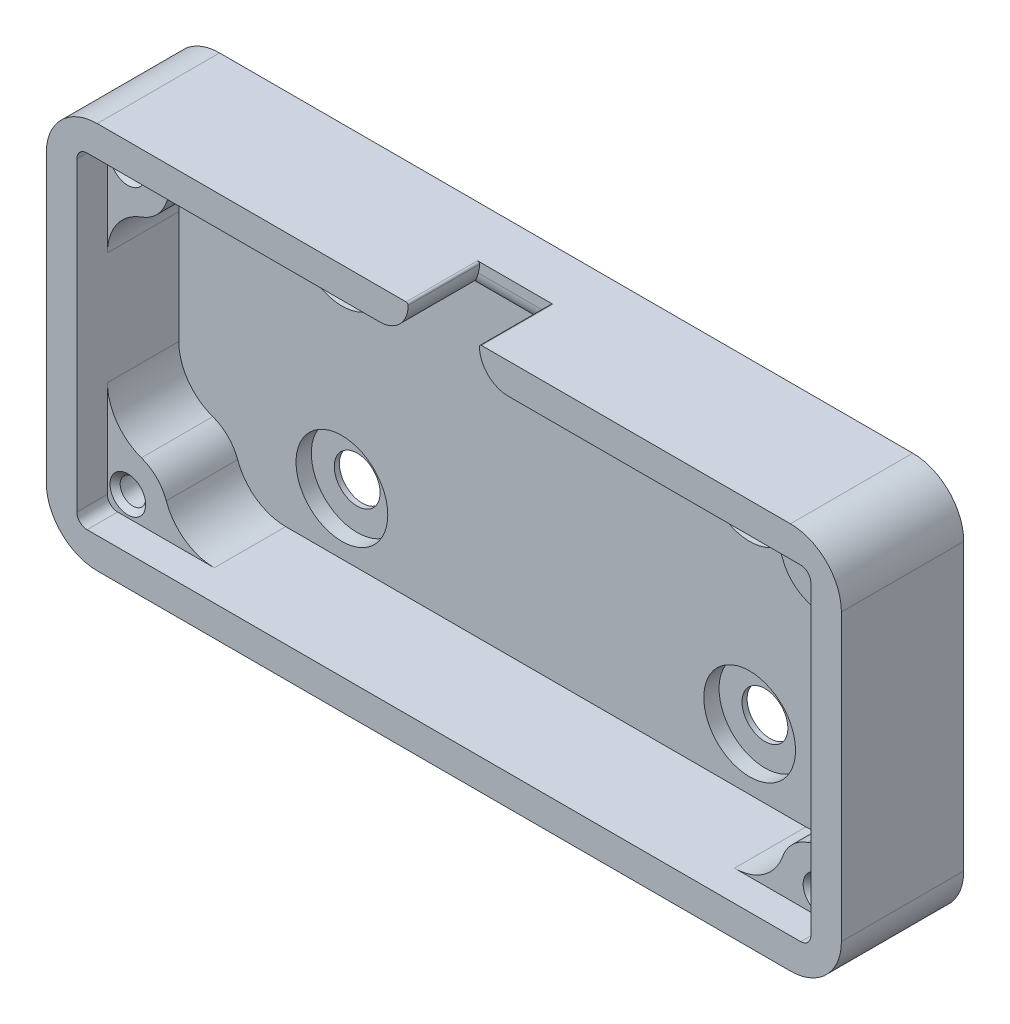
SolidWorks part; units mm, degrees
ref_plane "Piano frontale" through (0, 0, 0) normal (0, 0, 1) x (1, 0, 0)
ref_plane "Piano superiore" through (0, 0, 0) normal (0, 1, 0) x (1, 0, 0)
ref_plane "Piano destro" through (0, 0, 0) normal (1, 0, 0) x (0, 0, -1)
sketch "Schizzo1" plane through (0, 0, 0) normal (0, 0, 1) x (1, 0, 0)
  line L0 (-18.3021, 8.9164) -> (-39, 19) construction
  line L1 (36, 16) -> (-36, 16)
  line L2 (36, 16) -> (36, -16)
  line L3 (36, -16) -> (-36, -16)
  line L4 (-36, 16) -> (-36, -16)
  line L5 (36, 16) -> (19.0589, 8.4706) construction
  line L6 (36, -16) -> (-36, 16) construction
  line L7 (39, 19) -> (-39, 19)
  line L8 (39, 19) -> (39, -19)
  line L9 (39, -19) -> (-39, -19)
  line L10 (-39, 19) -> (-39, -19)
  line L11 (39, 19) -> (19.3371, 9.4206) construction
  line L12 (39, -19) -> (19.5274, -9.5133) construction
  line L13 (34, 14) -> (-34, 14)
  line L14 (34, 14) -> (34, -14)
  line L15 (34, -14) -> (-34, -14)
  line L16 (-34, 14) -> (-34, -14)
  line L17 (34, 14) -> (-34, -14) construction
  line L18 (34, -14) -> (-34, 14) construction
  line L24 (20, -10) -> (-20, -10) construction
  line L25 (20, -10) -> (20, 10) construction
  line L26 (20, 10) -> (-20, 10) construction
  line L27 (-18.8804, -9.1982) -> (-39, -19) construction
  line L28 (19.5274, -9.5133) -> (-18.3021, 8.9164) construction
  line L29 (19.3371, 9.4206) -> (-18.8804, -9.1982) construction
  line L30 (19.0589, 8.4706) -> (-36, -16) construction
  line L31 (-20, -10) -> (-20, 10) construction
  line L32 (20, -10) -> (-20, 10) construction
  line L33 (20, 10) -> (-20, -10) construction
  circle A0 centre (-34, 14) radius 1.25
  circle A1 centre (-34, -14) radius 1.25
  circle A2 centre (34, -14) radius 1.25
  circle A3 centre (34, 14) radius 1.25
  circle A8 centre (-20, 10) radius 2.25
  circle A9 centre (-20, -10) radius 2.25
  circle A10 centre (20, -10) radius 2.25
  circle A11 centre (20, 10) radius 2.25
  point P0 (0, 0)
  point P6 (0, 0)
  point P19 (0, 0)
  point P28 (1.4654, -0.5401)
  point P32 (0, 0)
  dimension "D5" = 2.5
  dimension "D10" = 4.5
  dimension "D1" = 72
  dimension "D2" = 32
  dimension "D3" = 3
  dimension "D4" = 3
  dimension "D6" = 2
  dimension "D7" = 2
  dimension "D8" = 20
  dimension "D9" = 40
extrude "Estrusione-Estrusione1" add sketch "Schizzo1" along normal blind 2 contours L7 L10 L9 L8 L4 L1 L2 L3 | L1 L4 L3 L2 A3 L14 A2 L15 A1 L16 A0 L13 | A3 L13 A0 L16 A1 L15 A2 L14 A11 A8 A9 A10 | A11 A10 A9 A8 | A8 | L14 L13 L16 L15 | A11 | A10 | A9 region at (35.2121, 0, 0) region at (38.1324, 0, 0) region at (0, 0, 0)
sketch "Schizzo2" plane through (0, 0, 2) normal (0, 0, 1) x (1, 0, 0)
  line L1 (-36, 16) -> (36, 16)
  line L2 (-36, 16) -> (-36, -16)
  line L3 (-36, -16) -> (36, -16)
  line L4 (39, 19) -> (-39, 19)
  line L5 (-39, 19) -> (-39, -19)
  line L6 (-39, -19) -> (39, -19)
  line L7 (39, -19) -> (39, 19)
  line L8 (39, 19) -> (-39, 19)
  line L9 (-39, 19) -> (-39, -19)
  line L10 (-39, -19) -> (39, -19)
  line L11 (39, -19) -> (39, 19)
  line L12 (36, 16) -> (36, -16)
  circle A0 centre (34, 14) radius 1.25 construction
  circle A1 centre (34, -14) radius 1.25 construction
  circle A2 centre (-34, -14) radius 1.25 construction
  circle A3 centre (-34, 14) radius 1.25 construction
  circle A4 centre (34, 14) radius 1.25
  circle A5 centre (34, -14) radius 1.25
  circle A6 centre (-34, -14) radius 1.25
  circle A7 centre (-34, 14) radius 1.25
  circle A8 centre (-34, 14) radius 4
  circle A9 centre (-34, -14) radius 4
  circle A10 centre (34, -14) radius 4
  circle A11 centre (34, 14) radius 4
  arc M9 (-34, 12.75) -> (-32.75, 14) centre (-34, 14) cw
  arc M10 (-32.75, -14) -> (-34, -12.75) centre (-34, -14) cw
  arc M11 (32.75, 14) -> (34, 12.75) centre (34, 14) cw
  arc M12 (34, -12.75) -> (32.75, -14) centre (34, -14) cw
  line M13 (39, 19) -> (-39, 19)
  line M14 (-39, 19) -> (-39, -19)
  line M15 (-39, -19) -> (39, -19)
  line M16 (39, -19) -> (39, 19)
  dimension "D6" = 8
  dimension "D2" = 3
  dimension "D3" = 3
  dimension "D4" = 3
  dimension "D5" = 3
  dimension "D1" = 0
extrude "Estrusione-Estrusione2" add sketch "Schizzo2" along normal blind 7 contours A11 L12 A10 L3 A9 L2 A8 L1 M16 M13 M14 M15 | L1 A8 L2 | L2 A8 L1 M9 | L3 A9 L2 M10 | L2 A9 L3 | L12 A10 L3 M12 | L3 A10 L12 | L1 A11 L12 M11 | L12 A11 L1 region at (-36.1056, 13.2679, 2) region at (-33.0905, 13.0905, 2) region at (35.008, 17.7617, 2) region at (33.0905, 13.0905, 2) region at (-33.0905, -13.0905, 2) region at (-36.1056, -13.2679, 2) region at (37.3727, -12.0528, 2) region at (33.0905, -13.0905, 2) region at (38.1324, 0, 2)
sketch "Schizzo3" plane through (0, 0, 9) normal (0, 0, 1) x (1, 0, 0)
  line L0 (36, 16) -> (36, -16) construction
  line L1 (-36, -16) -> (36, -16) construction
  line L2 (-36, 16) -> (-36, -16) construction
  line L3 (-36, 16) -> (36, 16) construction
  line L4 (36, 16) -> (36, -16)
  line L5 (-36, -16) -> (36, -16)
  line L6 (-36, 16) -> (-36, -16)
  line L7 (-36, 16) -> (36, 16)
  line L12 (39, -19) -> (39, 19)
  line L14 (39, -19) -> (39, 19)
  line L20 (39, 19) -> (-39, 19)
  line L22 (39, 19) -> (-39, 19)
  line L24 (-39, 19) -> (-39, -19)
  line L25 (-39, 19) -> (-39, -19)
  line L26 (-39, -19) -> (39, -19)
  line L27 (-39, -19) -> (39, -19)
  dimension "D1" = 0
extrude "Estrusione-Estrusione3" add sketch "Schizzo3" along normal blind 3
chamfer "Smusso1" distance 0.5 angle 45 4 edges at (35.25, 14, 9) (35.25, -14, 9) (-32.75, -14, 9) (-32.75, 14, 9)
fillet "Raccordo1" radius 5 4 edges at (-39, 19, 6) (-39, -19, 6) (39, 19, 6) (39, -19, 6)
sketch "Schizzo4" plane through (0, 0, 2) normal (0, 0, 1) x (1, 0, 0)
  circle A0 centre (-20, 10) radius 4.5
  circle A1 centre (20, 10) radius 4.5
  circle A2 centre (20, -10) radius 4.5
  circle A3 centre (-20, -10) radius 4.5
  dimension "D1" = 9
extrude "Taglio-Estrusione1" cut sketch "Schizzo4" against normal blind 1.5
fillet "Raccordo2" radius 5 8 edges at (30.5359, -16, 5.5) (36, -10.5359, 5.5) (36, 10.5359, 5.5) (30.5359, 16, 5.5) (-36, -10.5359, 5.5) (-30.5359, -16, 5.5) (-36, 10.5359, 5.5) (-30.5359, 16, 5.5)
fillet "Raccordo3" radius 1 4 edges at (36, -16, 10.5) (-36, -16, 10.5) (-36, 16, 10.5) (36, 16, 10.5)
sketch "Schizzo5" plane through (0, 19, 0) normal (0, 1, 0) x (1, 0, 0)
  line L0 (34, -12) -> (-34, -12) construction
  line L1 (3.5, -12) -> (-3.5, -12)
  line L2 (3.5, -12) -> (3.5, -5)
  line L3 (3.5, -5) -> (-3.5, -5)
  line L4 (-3.5, -12) -> (-3.5, -5)
  point P6 (0, -12)
  dimension "D1" = 7
  dimension "D2" = 7
extrude "Taglio-Estrusione2" cut sketch "Schizzo5" against normal up to next
fillet "Raccordo4" radius 2.8 2 edges at (-3.5, 16, 8.5) (3.5, 16, 8.5)
fillet "Raccordo5" radius 0.2 2 edges at (-3.5, 19, 8.5) (3.5, 19, 8.5)
fillet "Raccordo6" radius 2 1 edges at (0, 16, 5)
